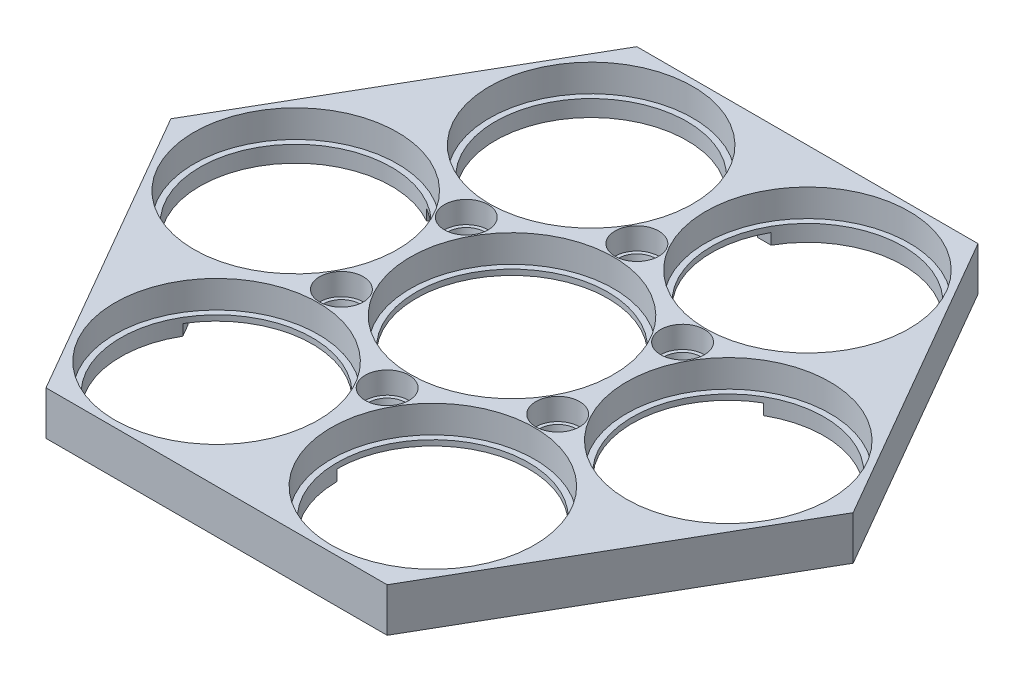
SolidWorks part; units mm, degrees
material "Malleable Cast Iron"
ref_plane "Front Plane" through (0, 0, 0) normal (0, 0, 1) x (1, 0, 0)
ref_plane "Top Plane" through (0, 0, 0) normal (0, 1, 0) x (1, 0, 0)
ref_plane "Right Plane" through (0, 0, 0) normal (1, 0, 0) x (0, 0, -1)
sketch "Sketch1" plane through (0, 0, 0) normal (0, 1, 0) x (1, 0, 0)
  line L0 (-22, 0) -> (-17.5, 0) construction
  line L1 (39.5, 0) -> (19.75, 34.208) construction
  line L2 (19.75, 34.208) -> (-19.75, 34.208) construction
  line L3 (-19.75, 34.208) -> (-39.5, 0) construction
  line L4 (-39.5, 0) -> (-19.75, -34.208) construction
  line L5 (-19.75, -34.208) -> (19.75, -34.208) construction
  line L6 (19.75, -34.208) -> (39.5, 0) construction
  line L7 (-19.75, 51.708) -> (-19.75, 53.958) construction
  line L8 (62.3053, 0) -> (31.1527, 53.958)
  line L9 (31.1527, 53.958) -> (-31.1527, 53.958)
  line L10 (-31.1527, 53.958) -> (-62.3053, 0)
  line L11 (-62.3053, 0) -> (-31.1527, -53.958)
  line L12 (-31.1527, -53.958) -> (31.1527, -53.958)
  line L13 (31.1527, -53.958) -> (62.3053, 0)
  line L14 (-19.75, 0) -> (-17.5, 0)
  circle A0 centre (0, 0) radius 17.5
  circle A1 centre (0, 0) radius 34.208 construction
  circle A2 centre (-19.75, 34.208) radius 17.5
  circle A3 centre (19.75, 34.208) radius 17.5
  circle A4 centre (39.5, 0) radius 17.5
  circle A5 centre (19.75, -34.208) radius 17.5
  circle A6 centre (-19.75, -34.208) radius 17.5
  circle A7 centre (-39.5, 0) radius 17.5
  circle A8 centre (0, 0) radius 53.958 construction
  dimension "D1" = 35
  dimension "D2" = 4.5
extrude "Boss-Extrude1" add sketch "Sketch1" along normal blind 1 contours L12 L13 L8 L9 L10 L11 A7 A6 A5 A4 A3 A2 A0 region at (45.3014, 0, 26.1548)
sketch "Sketch2" plane through (0, 1, 0) normal (0, 1, 0) x (1, 0, 0)
  line L1 (62.3053, 0) -> (31.1527, 53.958)
  line L2 (31.1527, 53.958) -> (-31.1527, 53.958)
  line L3 (-31.1527, 53.958) -> (-62.3053, 0)
  line L4 (-62.3053, 0) -> (-31.1527, -53.958)
  line L5 (-31.1527, -53.958) -> (31.1527, -53.958)
  line L6 (31.1527, -53.958) -> (62.3053, 0)
  circle A0 centre (-39.5, 0) radius 18.575
  circle A1 centre (-19.75, 34.208) radius 18.575
  circle A2 centre (19.75, 34.208) radius 18.575
  circle A3 centre (0, 0) radius 18.575
  circle A4 centre (39.5, 0) radius 18.575
  circle A5 centre (19.75, -34.208) radius 18.575
  circle A6 centre (-19.75, -34.208) radius 18.575
  circle A7 centre (0, 0) radius 53.958 construction
  dimension "D1" = 37.15
extrude "Boss-Extrude2" add sketch "Sketch2" along normal blind 5
sketch "Sketch3" plane through (0, 6, 0) normal (0, 1, 0) x (1, 0, 0)
  line L0 (-23.4136, 9.2875) -> (-19.75, 15.633) construction
  line L1 (-19.75, 15.633) -> (-16.0864, 9.2875) construction
  line L2 (-16.0864, 9.2875) -> (-23.4136, 9.2875) construction
  circle A0 centre (-19.75, 11.4027) radius 4
  circle A1 centre (19.75, 11.4027) radius 4
  circle A2 centre (0, -22.8053) radius 4
  circle A3 centre (-19.75, -11.4027) radius 4
  circle A4 centre (19.75, -11.4027) radius 4
  circle A5 centre (0, 0) radius 22.8053 construction
  circle A6 centre (-39.5, 0) radius 18.575 construction
  circle A7 centre (-19.75, 34.208) radius 18.575 construction
  circle A8 centre (0, 0) radius 18.575 construction
  circle A9 centre (0, 22.8053) radius 4
  dimension "D1" = 120
  dimension "D3" = 8
  dimension "D2" = 120
extrude "Cut-Extrude1" cut sketch "Sketch3" against normal blind 4 and the other way through all
extrude "Cut-Extrude2" cut sketch "Sketch3<2>" against normal through all draft 9 contours A0 | A1 | A2 | A3 | A4 | A9 region at (-19.75, 6, -11.4027) region at (19.75, 6, -11.4027) region at (0, 6, 22.8053) region at (-19.75, 6, 11.4027) region at (19.75, 6, 11.4027) region at (0, 6, -22.8053)
sketch "Sketch3<2>" plane through (0, 6, 0) normal (0, 1, 0) x (1, 0, 0) same geometry as "Sketch3"
sketch "Sketch4" plane through (0, 0, 0) normal (0, -1, 0) x (1, 0, 0)
  circle A0 centre (0, -22.8053) radius 4
  circle A1 centre (-19.75, 11.4027) radius 4
  circle A2 centre (19.75, 11.4027) radius 4
  circle A3 centre (0, 0) radius 22.8053 construction
  point P11 (19.75, -11.4027)
  dimension "D1" = 8
sketch "Sketch5" plane through (0, 0, 0) normal (0, -1, 0) x (1, 0, 0)
  line L0 (-62.3053, 0) -> (-31.1527, -53.958)
  line L1 (-31.1527, -53.958) -> (-62.3053, 0) construction
  line L3 (-28.5, -19.0526) -> (-30.75, -15.1554)
  line L4 (-62.3053, 0) -> (-57, 0)
  line L5 (-4.5074, -42.8053) -> (4.5074, -42.8053)
  line L6 (31.1527, -53.958) -> (28.5, -49.3634)
  line L7 (-31.1527, -53.958) -> (31.1527, -53.958)
  line L8 (31.1527, 53.958) -> (-31.1527, 53.958)
  line L9 (-2.25, 34.208) -> (2.25, 34.208)
  line L10 (31.1527, 53.958) -> (28.5, 49.3634)
  line L11 (-34.8168, 25.3062) -> (-39.3242, 17.4991)
  line L12 (-62.3053, 0) -> (-57, 0)
  line L13 (-31.1527, 53.958) -> (-62.3053, 0)
  line L14 (31.1527, -53.958) -> (62.3053, 0)
  line L15 (30.75, -15.1554) -> (28.5, -19.0526)
  line L16 (31.1527, -53.958) -> (28.5, -49.3634)
  line L17 (39.3242, 17.4991) -> (34.8168, 25.3062)
  line L18 (31.1527, 53.958) -> (28.5, 49.3634)
  line L19 (62.3053, 0) -> (31.1527, 53.958)
  circle A0 centre (-19.75, -34.208) radius 17.5 construction
  circle A2 centre (-39.5, 0) radius 17.5 construction
  arc A3 (-30.75, -15.1554) -> (-57, 0) centre (-39.5, 0) cw
  arc A4 (-4.5074, -42.8053) -> (-28.5, -19.0526) centre (-19.75, -34.208) cw
  circle A5 centre (19.75, -34.208) radius 17.5 construction
  arc A6 (4.5074, -42.8053) -> (28.5, -49.3634) centre (19.75, -34.208) ccw
  circle A7 centre (0, -22.8053) radius 3.0497 construction
  arc A8 (2.25, 34.208) -> (28.5, 49.3634) centre (19.75, 34.208) cw
  arc A9 (-34.8168, 25.3062) -> (-2.25, 34.208) centre (-19.75, 34.208) cw
  arc A10 (-39.3242, 17.4991) -> (-57, 0) centre (-39.5, 0) ccw
  arc A11 (28.5, -19.0526) -> (28.5, -49.3634) centre (19.75, -34.208) cw
  arc A12 (39.3242, 17.4991) -> (30.75, -15.1554) centre (39.5, 0) cw
  arc A13 (34.8168, 25.3062) -> (28.5, 49.3634) centre (19.75, 34.208) ccw
  point P55 (0, 0)
  circle M14 centre (-39.5, 0) radius 17.5
  circle M15 centre (-19.75, 34.208) radius 17.5
  circle M16 centre (19.75, 34.208) radius 17.5
  circle M17 centre (39.5, 0) radius 17.5
  circle M18 centre (19.75, -34.208) radius 17.5
  circle M19 centre (-19.75, -34.208) radius 17.5
  line M20 (31.1527, 53.958) -> (-31.1527, 53.958)
  line M21 (-31.1527, 53.958) -> (-62.3053, 0)
  line M22 (-62.3053, 0) -> (-31.1527, -53.958)
  line M23 (-31.1527, -53.958) -> (31.1527, -53.958)
  line M24 (31.1527, -53.958) -> (62.3053, 0)
  line M25 (62.3053, 0) -> (31.1527, 53.958)
  dimension "D1" = 20
  dimension "D2" = 3
extrude "Boss-Extrude3" add sketch "Sketch5" along normal blind 2 contours L11 L9 L10 L4 M15 M16 M20 M21 M14 | L6 L5 L3 L4 M23 M18 M19 M14 M22 | L17 L15 L6 L10 M17 M18 M24 M25 M16 region at (-59.6527, 0, -1.0792) region at (-45.7944, 0, 26.4394) region at (30.8057, 0, -51.0953)
sketch "Sketch6" plane through (0, -2, 0) normal (0, -1, 0) x (1, 0, 0)
  line L0 (-2, -42.8053) -> (2, -42.8053)
  line L5 (0, -45.8053) -> (-1, -47.5374) construction
  line L6 (-1, -47.5374) -> (1, -47.5374) construction
  line L7 (1, -47.5374) -> (0, -45.8053) construction
  line L10 (-4.5074, -42.8053) -> (4.5074, -42.8053) construction
  line L11 (-2, -42.8053) -> (-2, -47.5374)
  line L12 (2, -42.8053) -> (2, -47.5374)
  line L13 (-36.0705, 23.1347) -> (-38.0705, 19.6706)
  line L14 (-36.0705, 23.1347) -> (-40.1686, 25.5007)
  line L15 (-38.0705, 19.6706) -> (-42.1686, 22.0366)
  line L16 (-39.6686, 22.9027) -> (-40.6686, 24.6347) construction
  line L17 (-40.6686, 24.6347) -> (-41.6686, 22.9027) construction
  line L18 (-41.6686, 22.9027) -> (-39.6686, 22.9027) construction
  circle A0 centre (-1, -47.5374) radius 1
  circle A1 centre (1, -47.5374) radius 1
  circle A2 centre (0, -45.8053) radius 1
  circle A3 centre (-40.6686, 24.6347) radius 1
  circle A4 centre (-41.6686, 22.9027) radius 1
  circle A5 centre (-39.6686, 22.9027) radius 1
  point P15 (0, -42.8053)
  point P16 (0, -42.8053)
  point P26 (0, 0)
  point P40 (0, 0)
  line M5 (4.5074, -42.8053) -> (-4.5074, -42.8053)
  line M9 (-39.3242, 17.4991) -> (-34.8168, 25.3062)
  dimension "D1" = 2
  dimension "D2" = 4
  dimension "D3" = 3
  dimension "D4" = 2
extrude "Cut-Extrude5" cut sketch "Sketch6" against normal up to surface (2 mm away) contours A2 A1 L12 L11 A0 M5 | A2 A0 A1 | A2 | A5 A4 L15 L14 A3 M9 | A5 | A3 | A5 A3 A4 | A4 | A1 | A0 region at (0, -2, -44.5001) region at (0, -2, -46.96) region at (0, -2, -45.8053) region at (-38.5382, -2, 22.25) region at (-40.6686, -2, 24.6347) region at (-41.6686, -2, 22.9027) region at (-40.6686, -2, 23.48) region at (-39.6686, -2, 22.9027) up to face at (0, 0, 17.5)
